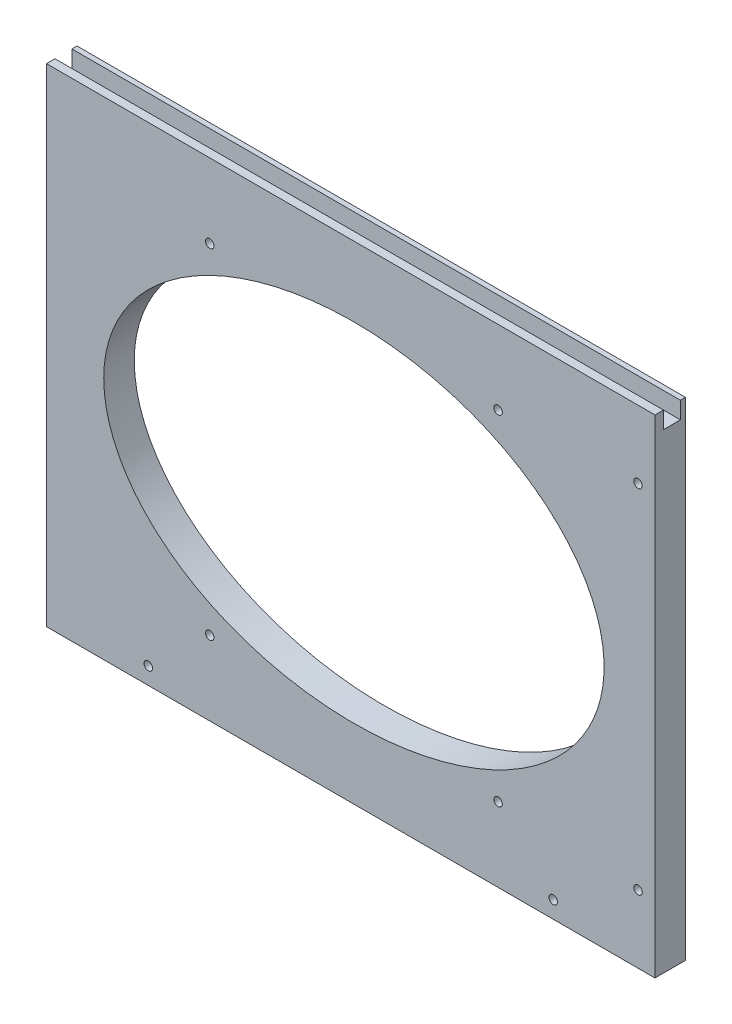
SolidWorks part; units mm, degrees
material "Pine"
ref_plane "Front Plane" through (0, 0, 0) normal (0, 0, 1) x (1, 0, 0)
ref_plane "Top Plane" through (0, 0, 0) normal (0, 1, 0) x (1, 0, 0)
ref_plane "Right Plane" through (0, 0, 0) normal (1, 0, 0) x (0, 0, -1)
sketch "Sketch1" plane through (0, 0, 0) normal (0, 0, 1) x (1, 0, 0)
  line L0 (-5300.6625, 1520.825) -> (-5451.475, 1520.825)
  line L1 (-5456.2375, 1384.3) -> (-5456.2375, 1516.0625)
  line L2 (-5557.8375, 1546.225) -> (-5194.3, 1546.225)
  line L3 (-5557.8375, 1539.875) -> (-5194.3, 1539.875)
  line L4 (-5297.4875, 1377.95) -> (-5454.65, 1377.95)
  line L5 (-5291.1375, 1384.3) -> (-5291.1375, 1516.0625)
  line L6 (-5300.6625, 1525.5875) -> (-5451.475, 1525.5875)
  line L7 (-5461, 1384.3) -> (-5461, 1516.0625)
  line L8 (-5297.4875, 1382.7125) -> (-5454.65, 1382.7125)
  line L9 (-5295.9, 1384.3) -> (-5295.9, 1516.0625)
  line L10 (-5740.4, 998.5375) -> (-5740.4, 1181.1)
  line L11 (-5740.4, 1181.1) -> (-5512.5938, 1181.1)
  line L12 (-5512.5938, 1181.1) -> (-5512.5938, 998.5375)
  line L13 (-5512.5938, 998.5375) -> (-5740.4, 998.5375)
  line L14 (-5258.5938, 1181.1) -> (-5486.4, 1181.1)
  line L15 (-5258.5938, 998.5375) -> (-5258.5938, 1181.1)
  line L16 (-5486.4, 998.5375) -> (-5258.5938, 998.5375)
  line L17 (-5486.4, 1181.1) -> (-5486.4, 998.5375)
  line L18 (-5740.4, 898.525) -> (-5011.7375, 898.525)
  line L19 (-5168.1062, 1384.3) -> (-5168.1062, 1392.2375)
  line L20 (-5176.0437, 1400.175) -> (-5245.8937, 1400.175)
  line L21 (-5253.8313, 1392.2375) -> (-5253.8313, 1384.3)
  line L22 (-5451.475, 1512.8875) -> (-5451.475, 1384.3)
  line L23 (-5303.8375, 1516.0625) -> (-5448.3, 1516.0625)
  line L24 (-5498.3062, 1384.3) -> (-5451.475, 1384.3)
  line L25 (-5253.8313, 1384.3) -> (-5300.6625, 1384.3)
  line L26 (-5584.0312, 1384.3) -> (-5740.4, 1384.3)
  line L27 (-5564.1875, 1536.7) -> (-5740.4, 1536.7)
  line L28 (-5740.4, 1357.3125) -> (-5740.4, 1206.5)
  line L29 (-5011.7375, 1357.3125) -> (-5740.4, 1357.3125)
  line L30 (-5011.7375, 1206.5) -> (-5011.7375, 1357.3125)
  line L31 (-5740.4, 1206.5) -> (-5011.7375, 1206.5)
  line L32 (-4765.675, 1549.4) -> (-4978.4, 1549.4)
  line L33 (-4765.675, 1397) -> (-4765.675, 1549.4)
  line L34 (-4978.4, 1397) -> (-4765.675, 1397)
  line L35 (-4978.4, 1549.4) -> (-4978.4, 1397)
  line L36 (-4765.675, 1371.6) -> (-4978.4, 1371.6)
  line L37 (-4765.675, 1219.2) -> (-4765.675, 1371.6)
  line L38 (-4978.4, 1219.2) -> (-4765.675, 1219.2)
  line L39 (-4978.4, 1371.6) -> (-4978.4, 1219.2)
  line L40 (-5284.7875, 803.275) -> (-5272.0875, 803.275)
  line L41 (-5187.95, 1536.7) -> (-5011.7375, 1536.7)
  line L42 (-5300.6625, 1384.3) -> (-5300.6625, 1512.8875)
  line L43 (-5740.4, 1536.7) -> (-5740.4, 1384.3)
  line L44 (-5557.8375, 1536.7) -> (-5557.8375, 1549.4)
  line L45 (-5557.8375, 1549.4) -> (-5194.3, 1549.4)
  line L46 (-5194.3, 1549.4) -> (-5194.3, 1536.7)
  line L47 (-5011.7375, 1536.7) -> (-5011.7375, 1384.3)
  line L48 (-5011.7375, 1384.3) -> (-5168.1062, 1384.3)
  line L49 (-5498.3062, 1384.3) -> (-5498.3062, 1392.2375)
  line L50 (-5506.2437, 1400.175) -> (-5576.0938, 1400.175)
  line L51 (-5584.0312, 1392.2375) -> (-5584.0312, 1384.3)
  line L52 (-5740.4, 660.4) -> (-5740.4, 898.525)
  line L53 (-5011.7375, 898.525) -> (-5011.7375, 660.4)
  line L54 (-5011.7375, 660.4) -> (-5740.4, 660.4)
  line L55 (-5291.1375, 803.275) -> (-5291.1375, 752.475)
  line L56 (-5265.7375, 752.475) -> (-5265.7375, 803.275)
  line L57 (-5284.7875, 752.475) -> (-5272.0875, 752.475)
  arc A0 (-5451.475, 1520.825) -> (-5456.2375, 1516.0625) centre (-5451.475, 1516.0625) ccw
  arc A1 (-5461, 1384.3) -> (-5454.65, 1377.95) centre (-5454.65, 1384.3) ccw
  arc A2 (-5297.4875, 1377.95) -> (-5291.1375, 1384.3) centre (-5297.4875, 1384.3) ccw
  circle A3 centre (-5037.9312, 1233.4875) radius 1.5875
  circle A4 centre (-5037.9312, 1328.7375) radius 1.5875
  circle A5 centre (-5714.2063, 1233.4875) radius 1.5875
  circle A6 centre (-5714.2063, 1328.7375) radius 1.5875
  circle A7 centre (-5018.0875, 1333.5) radius 1.5875
  circle A8 centre (-5018.0875, 1231.9) radius 1.5875
  circle A9 centre (-5734.05, 1231.9) radius 1.5875
  circle A10 centre (-5734.05, 1333.5) radius 1.5875
  circle A11 centre (-5734.05, 1511.3) radius 1.5875
  circle A12 centre (-5734.05, 1409.7) radius 1.5875
  circle A13 centre (-5018.0875, 1511.3) radius 1.5875
  circle A14 centre (-5018.0875, 1409.7) radius 1.5875
  arc A15 (-5557.8375, 1546.225) -> (-5557.8375, 1539.875) centre (-5557.8375, 1543.05) ccw
  arc A16 (-5194.3, 1539.875) -> (-5194.3, 1546.225) centre (-5194.3, 1543.05) ccw
  arc A17 (-5291.1375, 1516.0625) -> (-5300.6625, 1525.5875) centre (-5300.6625, 1516.0625) ccw
  arc A18 (-5451.475, 1525.5875) -> (-5461, 1516.0625) centre (-5451.475, 1516.0625) ccw
  arc A19 (-5456.2375, 1384.3) -> (-5454.65, 1382.7125) centre (-5454.65, 1384.3) ccw
  arc A20 (-5297.4875, 1382.7125) -> (-5295.9, 1384.3) centre (-5297.4875, 1384.3) ccw
  arc A21 (-5295.9, 1516.0625) -> (-5300.6625, 1520.825) centre (-5300.6625, 1516.0625) ccw
  circle A22 centre (-5702.3, 892.175) radius 1.5875
  circle A23 centre (-5734.05, 860.425) radius 1.5875
  circle A24 centre (-5474.8906, 892.175) radius 1.5875
  circle A25 centre (-5277.2469, 892.175) radius 1.5875
  circle A26 centre (-5049.8375, 892.175) radius 1.5875
  circle A27 centre (-5018.0875, 860.425) radius 1.5875
  circle A28 centre (-5296.6938, 1174.75) radius 1.5875
  circle A29 centre (-5448.3, 1174.75) radius 1.5875
  circle A30 centre (-5264.9437, 1155.7) radius 1.5875
  circle A31 centre (-5264.9437, 1023.9375) radius 1.5875
  circle A32 centre (-5518.9438, 1155.7) radius 1.5875
  circle A33 centre (-5518.9438, 1023.9375) radius 1.5875
  circle A34 centre (-5702.3, 1004.8875) radius 1.5875
  circle A35 centre (-5550.6937, 1004.8875) radius 1.5875
  arc A36 (-5576.0938, 1400.175) -> (-5584.0312, 1392.2375) centre (-5576.0938, 1392.2375) ccw
  arc A37 (-5168.1062, 1392.2375) -> (-5176.0437, 1400.175) centre (-5176.0437, 1392.2375) ccw
  arc A38 (-5245.8937, 1400.175) -> (-5253.8313, 1392.2375) centre (-5245.8937, 1392.2375) ccw
  arc A39 (-5448.3, 1516.0625) -> (-5451.475, 1512.8875) centre (-5448.3, 1512.8875) ccw
  arc A40 (-5284.7875, 803.275) -> (-5291.1375, 803.275) centre (-5287.9625, 803.275) ccw
  circle A41 centre (-5679.2812, 1026.3187) radius 1.5875
  circle A42 centre (-5679.2812, 1153.3187) radius 1.5875
  circle A43 centre (-5571.3313, 1153.3187) radius 1.5875
  circle A44 centre (-5571.3313, 1026.3187) radius 1.5875
  circle A45 centre (-5317.3312, 1153.3187) radius 1.5875
  circle A46 centre (-5317.3312, 1026.3187) radius 1.5875
  circle A47 centre (-5425.2812, 1026.3187) radius 1.5875
  circle A48 centre (-5425.2812, 1153.3187) radius 1.5875
  arc A49 (-5194.3, 1536.7) -> (-5187.95, 1536.7) centre (-5191.125, 1536.7) ccw
  arc A50 (-5564.1875, 1536.7) -> (-5557.8375, 1536.7) centre (-5561.0125, 1536.7) ccw
  arc A51 (-5300.6625, 1512.8875) -> (-5303.8375, 1516.0625) centre (-5303.8375, 1512.8875) ccw
  arc A52 (-5498.3062, 1392.2375) -> (-5506.2437, 1400.175) centre (-5506.2437, 1392.2375) ccw
  circle A53 centre (-5712.46, 784.225) radius 4.7625
  arc A54 (-5272.0875, 752.475) -> (-5265.7375, 752.475) centre (-5268.9125, 752.475) ccw
  arc A55 (-5291.1375, 752.475) -> (-5284.7875, 752.475) centre (-5287.9625, 752.475) ccw
  circle A56 centre (-5182.3938, 684.2125) radius 3.175
  circle A57 centre (-5239.5437, 684.2125) radius 3.175
  circle A58 centre (-5512.5938, 684.2125) radius 3.175
  circle A59 centre (-5569.7437, 684.2125) radius 3.175
  circle A60 centre (-5474.8906, 666.75) radius 1.5875
  circle A61 centre (-5277.2469, 666.75) radius 1.5875
  circle A62 centre (-5734.05, 698.5) radius 1.5875
  circle A63 centre (-5702.3, 666.75) radius 1.5875
  circle A64 centre (-5049.8375, 666.75) radius 1.5875
  circle A65 centre (-5018.0875, 698.5) radius 1.5875
  circle A66 centre (-5713.73, 835.025) radius 4.7625
  circle A67 centre (-5712.46, 819.785) radius 4.7625
  circle A68 centre (-5712.46, 802.005) radius 4.7625
  circle A69 centre (-5714.2063, 1314.45) radius 3.175
  circle A70 centre (-5037.9312, 1314.45) radius 3.175
  arc A71 (-5265.7375, 803.275) -> (-5272.0875, 803.275) centre (-5268.9125, 803.275) ccw
  ellipse E0 centre (-5371.3062, 1089.8188) end of major axis (-5277.6438, 1089.8188) minor radius 65.0875
  ellipse E1 centre (-5625.3062, 1089.8188) end of major axis (-5531.6438, 1089.8188) minor radius 65.0875
sketch "SpeakerMounting" plane through (0, 0, 0) normal (0, 0, 1) x (1, 0, 0)
  line L0 (-5512.5938, 998.5375) -> (-5512.5938, 1181.1)
  line L1 (-5512.5938, 1181.1) -> (-5740.4, 1181.1)
  line L2 (-5740.4, 1181.1) -> (-5740.4, 998.5375)
  line L3 (-5740.4, 998.5375) -> (-5512.5938, 998.5375)
extrude "SpeakerMounting_Thickness" add sketch "SpeakerMounting" against normal blind 11.43
sketch "SpeakerCutout" plane through (0, 0, 0) normal (0, 0, 1) x (1, 0, 0)
  line L0 (-5625.3062, 1154.9062) -> (-5625.3062, 1024.7313) construction
  line L1 (-5718.9687, 1089.8188) -> (-5531.6438, 1089.8188) construction
  circle A0 centre (-5571.3313, 1153.3187) radius 1.5875
  circle A1 centre (-5518.9438, 1155.7) radius 1.5875
  circle A2 centre (-5518.9438, 1023.9375) radius 1.5875
  circle A3 centre (-5550.6937, 1004.8875) radius 1.5875
  circle A4 centre (-5571.3313, 1026.3187) radius 1.5875
  circle A5 centre (-5679.2812, 1026.3187) radius 1.5875
  circle A6 centre (-5702.3, 1004.8875) radius 1.5875
  circle A7 centre (-5679.2812, 1153.3187) radius 1.5875
  ellipse E0 centre (-5625.3062, 1089.8188) end of major axis (-5718.9687, 1089.8188) minor radius 65.0875
extrude "Cut-Extrude1" cut sketch "SpeakerCutout" against normal up to surface (11.43 mm away) up to face at (-5626.4969, 1089.8188, -11.43)
sketch "SpeakerSlotForScreen" plane through (-5512.5938, 0, 0) normal (1, 0, 0) x (0, 0, -1)
  line L0 (5.715, 1181.1) -> (3.175, 1181.1)
  line L1 (11.43, 1181.1) -> (0, 1181.1) construction
  line L2 (3.175, 1181.1) -> (3.175, 1174.75)
  line L3 (3.175, 1174.75) -> (9.525, 1174.75)
  line L4 (9.525, 1174.75) -> (9.525, 1181.1)
  line L5 (9.525, 1181.1) -> (5.715, 1181.1)
extrude "Cut-Extrude2" cut sketch "SpeakerSlotForScreen" against normal up to surface (227.8063 mm away) up to face at (-5740.4, 1089.8188, -5.715)
